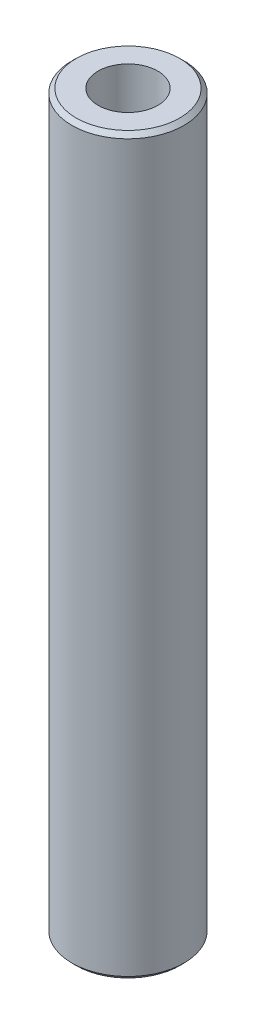
SolidWorks part; units mm, degrees
ref_plane "Front Plane" through (0, 0, 0) normal (0, 0, 1) x (1, 0, 0)
ref_plane "Top Plane" through (0, 0, 0) normal (0, 1, 0) x (1, 0, 0)
ref_plane "Right Plane" through (0, 0, 0) normal (1, 0, 0) x (0, 0, -1)
sketch "Sketch1" plane through (0, 0, 0) normal (0, 1, 0) x (1, 0, 0)
  circle A0 centre (0, 0) radius 45
  dimension "SHAFT_OD" = 90
extrude "Boss-Extrude1" add sketch "Sketch1" along normal blind 589.3457
sketch "Sketch2" plane through (0, 0, 0) normal (0, 1, 0) x (1, 0, 0)
  circle A0 centre (0, 0) radius 23.9355
  dimension "BORE_D" = 47.871
extrude "Cut-Extrude1" cut sketch "Sketch2" along normal through all
chamfer "Chamfer1" distance 3.3958 angle 45.671 2 edges at (0, 589.3457, 45) (0, 0, 45) first distance on face at (0, 589.3457, 45) first distance on face at (0, 0, 23.9355)
